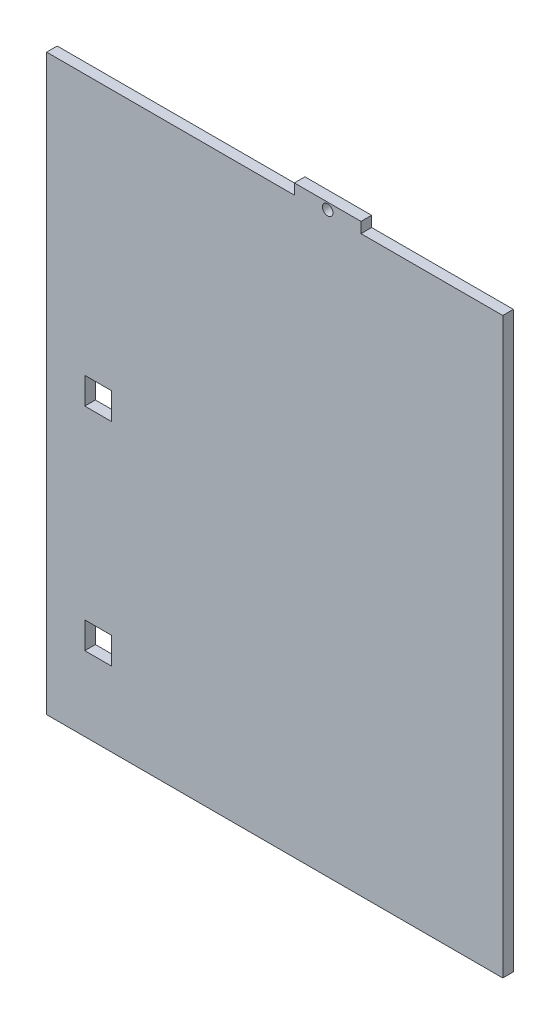
SolidWorks part; units mm, degrees
ref_plane "Front Plane" through (0, 0, 0) normal (0, 0, 1) x (1, 0, 0)
ref_plane "Top Plane" through (0, 0, 0) normal (0, 1, 0) x (1, 0, 0)
ref_plane "Right Plane" through (0, 0, 0) normal (1, 0, 0) x (0, 0, -1)
sketch "Sketch1" plane through (0, 0, 0) normal (0, 0, 1) x (1, 0, 0)
  line L1 (-68.425, 87.655) -> (68.425, 87.655)
  line L2 (-68.425, 87.655) -> (-68.425, -87.655)
  line L3 (-68.425, -87.655) -> (68.425, -87.655)
  line L4 (68.425, 87.655) -> (68.425, -87.655)
  line L5 (-68.425, 87.655) -> (68.425, -87.655) construction
  line L6 (-68.425, -87.655) -> (68.425, 87.655) construction
  point P0 (0, 0)
  dimension "D1" = 136.85
  dimension "D2" = 175.31
extrude "Boss-Extrude1" add sketch "Sketch1" along normal blind 3.18
sketch "Sketch2" plane through (0, 0, 3.18) normal (0, 0, 1) x (1, 0, 0)
  line L0 (-90.8369, -1.7668) -> (-82.8369, -1.7668) construction
  line L1 (-56.9833, 6.2332) -> (-48.9833, 6.2332)
  line L2 (-56.9833, 6.2332) -> (-56.9833, -1.7668)
  line L3 (-56.9833, -1.7668) -> (-48.9833, -1.7668)
  line L4 (-48.9833, 6.2332) -> (-48.9833, -1.7668)
  line L5 (-56.9833, 6.2332) -> (-48.9833, -1.7668) construction
  line L6 (-56.9833, -1.7668) -> (-48.9833, 6.2332) construction
  line L7 (-56.9833, -57.3115) -> (-48.9833, -57.3115)
  line L8 (-56.9833, -57.3115) -> (-56.9833, -65.3115)
  line L9 (-56.9833, -65.3115) -> (-48.9833, -65.3115)
  line L10 (-48.9833, -57.3115) -> (-48.9833, -65.3115)
  line L11 (-56.9833, -57.3115) -> (-48.9833, -65.3115) construction
  line L12 (-56.9833, -65.3115) -> (-48.9833, -57.3115) construction
  line L13 (-83.1084, -57.3115) -> (-91.1084, -57.3115) construction
  point P0 (-52.9833, 2.2332)
  point P5 (-52.9833, -61.3115)
  dimension "D1" = 8
  dimension "D2" = 8
  dimension "D3" = 8
  dimension "D4" = 8
extrude "Cut-Extrude1" cut sketch "Sketch2" against normal through all
sketch "Sketch3" plane through (0, 0, 3.18) normal (0, 0, 1) x (1, 0, 0)
  line L0 (68.425, 87.655) -> (-68.425, 87.655) construction
  line L1 (-68.425, 87.655) -> (5.895, 87.655)
  line L2 (-68.425, 87.655) -> (-68.425, 84.475)
  line L3 (-68.425, 84.475) -> (5.895, 84.475)
  line L4 (5.895, 87.655) -> (5.895, 84.475)
  line L5 (25.895, 84.475) -> (68.425, 84.475)
  line L6 (25.895, 84.475) -> (25.895, 87.655)
  line L7 (25.895, 87.655) -> (68.425, 87.655)
  line L8 (68.425, 84.475) -> (68.425, 87.655)
  circle A0 centre (15.8995, 85.655) radius 1.59
  dimension "D2" = 3.18
  dimension "D1" = 2
extrude "Cut-Extrude2" cut sketch "Sketch3" against normal blind 10
